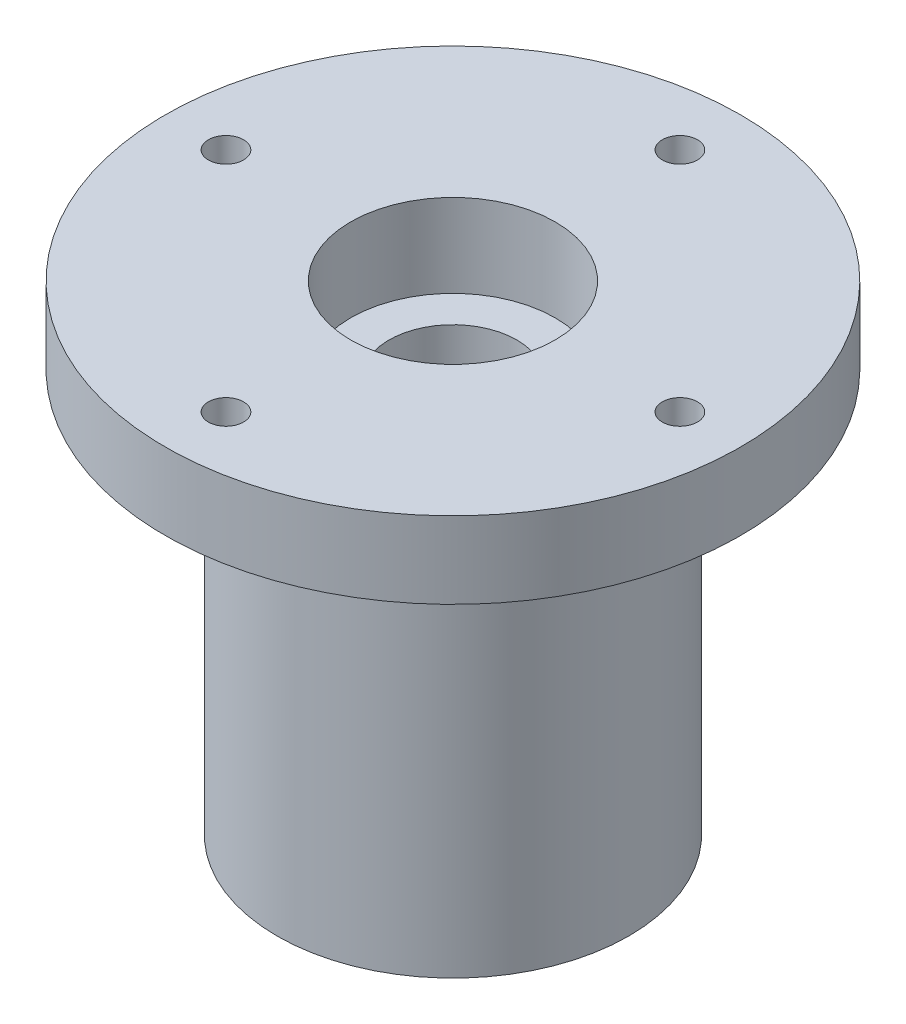
SolidWorks part; units mm, degrees
ref_plane "Front Plane" through (0, 0, 0) normal (0, 0, 1) x (1, 0, 0)
ref_plane "Top Plane" through (0, 0, 0) normal (0, 1, 0) x (1, 0, 0)
ref_plane "Right Plane" through (0, 0, 0) normal (1, 0, 0) x (0, 0, -1)
ref_axis "X" through (-88.99, 0, 0) along (1, 0, 0)
ref_axis "Y" through (0, 0, -88.99) along (0, 0, 1)
ref_axis "Z" through (0, 55, 0) along (0, -1, 0)
sketch "Sketch1" plane through (0, 0, 0) normal (0, 0, 1) x (1, 0, 0)
  line L0 (0, 0) -> (0, 49) construction
  line L1 (-45, 0) -> (-16, 0)
  line L2 (-16, 0) -> (-16, -13)
  line L3 (-16, -13) -> (-10, -13)
  line L4 (-10, -13) -> (-10, -62)
  line L5 (-10, -62) -> (-16, -62)
  line L6 (-16, -62) -> (-16, -75)
  line L7 (-16, -75) -> (-27.5, -75)
  line L8 (-27.5, -75) -> (-27.5, -12)
  line L9 (-27.5, -12) -> (-45, -12)
  line L10 (-45, -12) -> (-45, 0)
  dimension "D1" = 32
  dimension "D2" = 13
  dimension "D3" = 12
  dimension "D4" = 20
  dimension "D5" = 13
  dimension "D6" = 75
  dimension "D7" = 90
  dimension "D8" = 55
  dimension "D9" = 11.5
revolve "Revolve1" add sketch "Sketch1" angle 360 about L0
hole_wizard "M5 Clearance Hole1" positions "Sketch2" profile "Sketch3" hole size "M5" standard "DIN" end condition through all
sketch "Sketch2" plane through (0, -12, 0) normal (0, -1, 0) x (-1, 0, 0)
  circle A0 centre (0, 0) radius 35.5
  point P5 (0, -35.5)
  point P7 (35.5, 0)
  point P9 (0, 35.5)
  point P11 (-35.5, 0)
  dimension "D1" = 71
sketch "Sketch3" plane through (35.5, -12, 0) normal (1, 0, 0) x (0, 0, -1)
  line L0 (0, 0) -> (0, 12)
  line L1 (0, 12) -> (2.75, 12)
  line L2 (2.75, 12) -> (2.75, 3.25)
  line L3 (2.75, 3.25) -> (6, 0)
  line L5 (6, 0) -> (0, 0)
  line L6 (-2.75, 3.25) -> (-6, 0) construction
  line L11 (0, -6.35) -> (0, 107.95) construction
  dimension "Thru Hole Dia." = 5.5
  dimension "Thru Hole Depth" = 12
  dimension "Near C'Sink Dia." = 12
  dimension "Near C'Sink Angle" = 90
